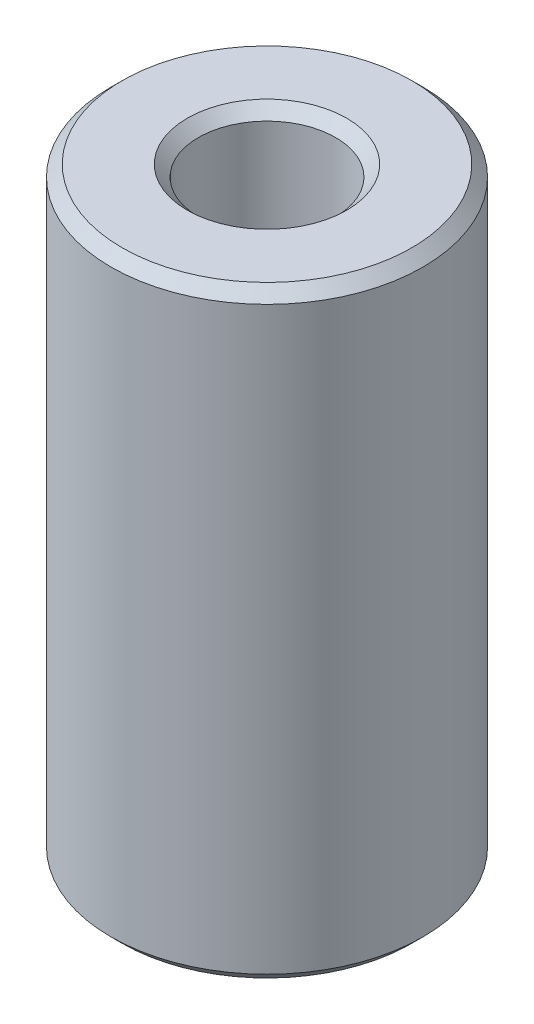
SolidWorks part; units mm, degrees
ref_plane "Front Plane" through (0, 0, 0) normal (0, 0, 1) x (1, 0, 0)
ref_plane "Top Plane" through (0, 0, 0) normal (0, 1, 0) x (1, 0, 0)
ref_plane "Right Plane" through (0, 0, 0) normal (1, 0, 0) x (0, 0, -1)
sketch "Sketch1" plane through (0, 0, 0) normal (0, 1, 0) x (1, 0, 0)
  circle A0 centre (0, 0) radius 7.5
  dimension "SLEEVE_OD" = 15
extrude "Boss-Extrude1" add sketch "Sketch1" along normal blind 28.9715
sketch "Sketch2" plane through (0, 0, 0) normal (0, 1, 0) x (1, 0, 0)
  circle A0 centre (0, 0) radius 3.2989
  dimension "BORE_D" = 6.5978
extrude "Cut-Extrude1" cut sketch "Sketch2" along normal through all
chamfer "Chamfer1" distance 0.5358 angle 45 4 edges at (0, 28.9715, 3.2989) (0, 0, 3.2989) (0, 0, 7.5) (0, 28.9715, 7.5)
